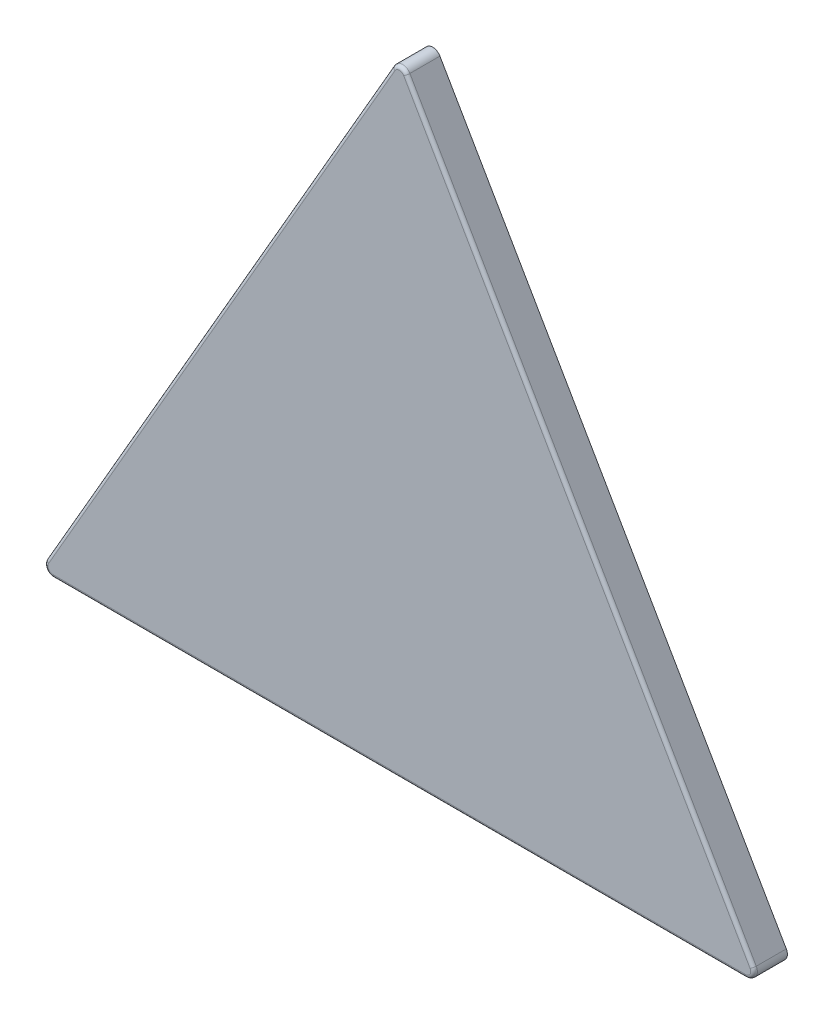
SolidWorks part; units mm, degrees
ref_plane "Plan de face" through (0, 0, 0) normal (0, 0, 1) x (1, 0, 0)
ref_plane "Plan de dessus" through (0, 0, 0) normal (0, 1, 0) x (1, 0, 0)
ref_plane "Plan de droite" through (0, 0, 0) normal (1, 0, 0) x (0, 0, -1)
sketch "Esquisse1" plane through (0, 0, 0) normal (0, 0, 1) x (1, 0, 0)
  line L0 (106.1378, -88.039) -> (2.298, 91.8167)
  line L1 (-2.0321, 91.8167) -> (-105.8719, -88.039)
  line L2 (-103.7068, -91.789) -> (103.9727, -91.789)
  arc A0 (103.9727, -91.789) -> (106.1378, -88.039) centre (103.9727, -89.289) ccw
  arc A1 (2.298, 91.8167) -> (-2.0321, 91.8167) centre (0.1329, 90.5667) ccw
  arc A2 (-105.8719, -88.039) -> (-103.7068, -91.789) centre (-103.7068, -89.289) ccw
  circle A3 centre (0.1329, 89.7508) radius 2.75
  circle A4 centre (103.2661, -88.881) radius 2.75
  circle A5 centre (-103.0002, -88.881) radius 2.75
extrude "Boss.-Extru.1" add sketch "Esquisse1" along normal blind 10 contours L0 A1 L1 A2 L2 A0
sketch "Esquisse2" plane through (0, 0, 0) normal (0, 0, -1) x (-1, 0, 0)
  line L3 (-52.4858, 0.8889) -> (100.0262, -87.164) construction
  line L4 (133.9055, -106.7242) -> (-0.1329, -91.789) construction
  line L5 (103.7068, -91.789) -> (-103.9727, -91.789) construction
  line L6 (-103.9727, -89.789) -> (103.7068, -89.789)
  line L7 (104.1398, -89.039) -> (0.3001, 90.8167)
  line L8 (-0.566, 90.8167) -> (-104.4057, -89.039)
  line L9 (-95.7454, -89.789) -> (95.4796, -89.789)
  line L10 (100.0262, -81.914) -> (4.4137, 83.6917)
  line L11 (-4.6796, 83.6917) -> (-100.2921, -81.914)
  line L12 (-0.1329, -91.789) -> (-0.1329, 86.3167) construction
  line L13 (-0.1329, 104.4568) -> (52.2199, 0.8889) construction
  line L14 (52.2199, 0.8889) -> (-100.2921, -87.164) construction
  line L15 (-0.1329, 91.0667) -> (-0.1329, 104.4568) construction
  arc A3 (95.4796, -89.789) -> (100.0262, -81.914) centre (95.4796, -84.539) ccw
  arc A4 (-4.6796, 83.6917) -> (4.4137, 83.6917) centre (-0.1329, 81.0667) cw
  arc A5 (-95.7454, -89.789) -> (-100.2921, -81.914) centre (-95.7454, -84.539) cw
  arc A6 (-104.4057, -89.039) -> (-103.9727, -89.789) centre (-103.9727, -89.289) ccw
  arc A7 (103.7068, -89.789) -> (104.1398, -89.039) centre (103.7068, -89.289) ccw
  arc A8 (0.3001, 90.8167) -> (-0.566, 90.8167) centre (-0.1329, 90.5667) ccw
  dimension "D1" = 2
extrude "Enlèv. mat.-Extru.2" cut sketch "Esquisse2" against normal blind 9.4
sketch "Esquisse4" plane through (0, 0, 10) normal (0, 0, 1) x (1, 0, 0)
  line L6 (104.4057, -89.039) -> (0.566, 90.8167)
  line L7 (-0.3001, 90.8167) -> (-104.1398, -89.039)
  line L8 (-103.7068, -89.789) -> (103.9727, -89.789)
  line L9 (104.4057, -89.039) -> (0.566, 90.8167)
  line L10 (-0.3001, 90.8167) -> (-104.1398, -89.039)
  line L11 (-103.7068, -89.789) -> (103.9727, -89.789)
  arc A6 (103.9727, -89.789) -> (104.4057, -89.039) centre (103.9727, -89.289) ccw
  arc A7 (0.566, 90.8167) -> (-0.3001, 90.8167) centre (0.1329, 90.5667) ccw
  arc A8 (-104.1398, -89.039) -> (-103.7068, -89.789) centre (-103.7068, -89.289) ccw
  arc A9 (103.9727, -89.789) -> (104.4057, -89.039) centre (103.9727, -89.289) ccw
  arc A10 (0.566, 90.8167) -> (-0.3001, 90.8167) centre (0.1329, 90.5667) ccw
  arc A11 (-104.1398, -89.039) -> (-103.7068, -89.789) centre (-103.7068, -89.289) ccw
  dimension "D1" = 2
extrude "Enlèv. mat.-Extru.4" cut sketch "Esquisse4" against normal blind 7 from offset 0.6 offset against normal yes
sketch "Esquisse5" plane through (0, 0, 0) normal (0, 0, -1) x (-1, 0, 0)
  circle A0 centre (-0.1329, 89.7508) radius 2.75 construction
  circle A1 centre (103.0002, -88.881) radius 2.75 construction
  circle A2 centre (-103.2661, -88.881) radius 2.75 construction
  circle A3 centre (-0.1329, 89.7508) radius 2.75
  circle A4 centre (103.0002, -88.881) radius 2.75
  circle A5 centre (-103.2661, -88.881) radius 2.75
extrude "Enlèv. mat.-Extru.5" cut sketch "Esquisse5" against normal blind 1
fillet "Congé1" radius 1 6 edges at (0.1329, -91.789, 10) (-105.8719, -90.539, 10) (-53.952, 1.8889, 10) (0.1329, 93.0667, 10) (54.2179, 1.8889, 10) (106.1378, -90.539, 10)
